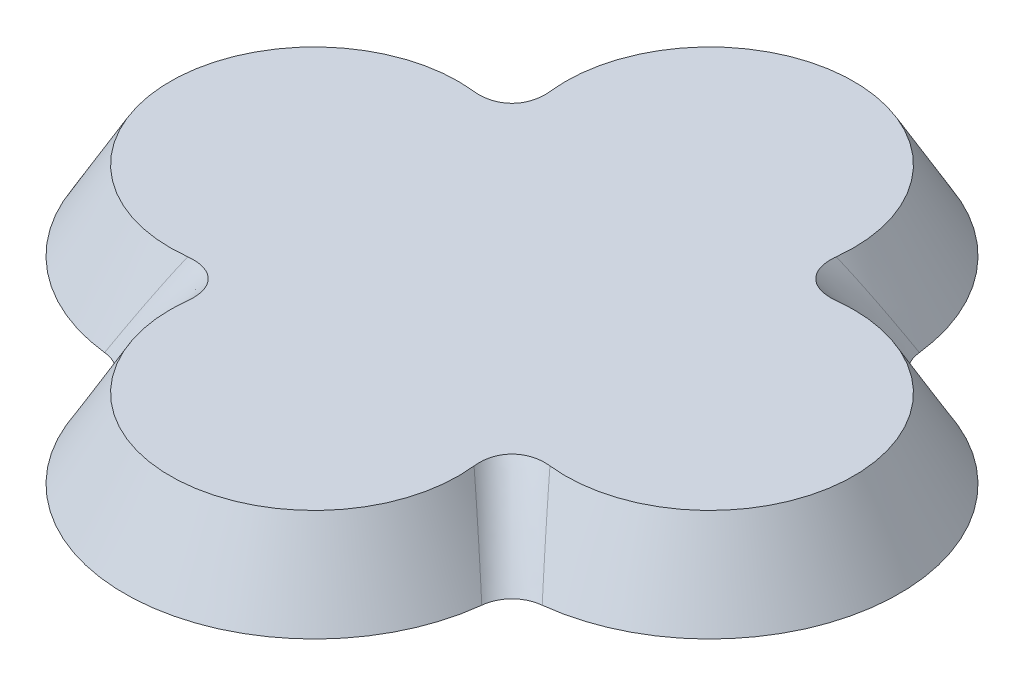
SolidWorks part; units mm, degrees
ref_plane "Front Plane" through (0, 0, 0) normal (0, 0, 1) x (1, 0, 0)
ref_plane "Top Plane" through (0, 0, 0) normal (0, 1, 0) x (1, 0, 0)
ref_plane "Right Plane" through (0, 0, 0) normal (1, 0, 0) x (0, 0, -1)
sketch "Sketch1" plane through (0, 0, 0) normal (0, 1, 0) x (1, 0, 0)
  line L0 (-12.7, 0) -> (12.7, 0) construction
  line L4 (-25.4, 25.4) -> (25.4, 25.4) construction
  line L5 (-25.4, 25.4) -> (-25.4, -25.4) construction
  line L6 (-25.4, -25.4) -> (25.4, -25.4) construction
  line L7 (25.4, 25.4) -> (25.4, -25.4) construction
  line L8 (-12.192, 12.192) -> (25.4, -25.4) construction
  line L9 (-25.4, -25.4) -> (12.192, 12.192) construction
  line L11 (0, 12.7) -> (0, -12.7) construction
  arc A7 (-12.1809, 12.1809) -> (-12.1809, -12.1809) centre (-12.7, 0) ccw
  arc A8 (12.1809, -12.1809) -> (12.1809, 12.1809) centre (12.7, 0) ccw
  arc A9 (12.1809, 12.1809) -> (-12.1809, 12.1809) centre (0, 12.7) ccw
  arc A10 (-12.1809, -12.1809) -> (12.1809, -12.1809) centre (0, -12.7) ccw
  point P3 (0, 0)
  point P5 (-9.2323, -11.6884)
  point P8 (0, 0)
  point P15 (0, 0)
  point P20 (0, 0)
  point P22 (0, 0)
  point P23 (-12.0016, -10.5538)
  point P24 (12.0654, -10.9474)
  point P26 (-12.07, 10.9794)
  point P27 (-10.168, 11.9262)
  point P29 (11.3076, -12.1122)
  point P30 (11.9599, 10.3321)
  point P31 (10.4113, 11.9752)
  dimension "D3" = 25.4
  dimension "D4" = 25.4
  dimension "D5" = 34.4529
  dimension "D6" = 12.192
  dimension "D7" = 17.9605
  dimension "D1" = 50.8
  dimension "D2" = 50.8
extrude "Boss-Extrude1" add sketch "Sketch1" along normal blind 5.08 draft 30
fillet "Fillet1" radius 2.54 4 edges at (9.8123, 3.401, -9.8123) (-9.8123, 3.401, -9.8123) (-9.8123, 3.401, 9.8123) (9.8123, 3.401, 9.8123)
